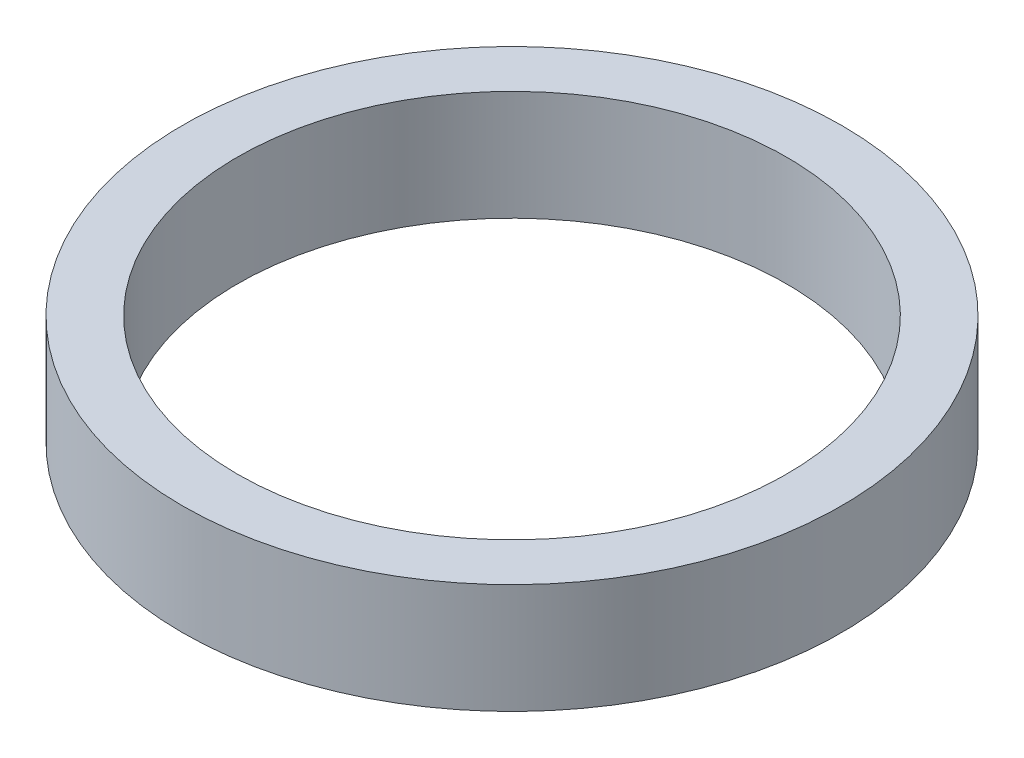
SolidWorks part; units mm, degrees
ref_plane "Front Plane" through (0, 0, 0) normal (0, 0, 1) x (1, 0, 0)
ref_plane "Top Plane" through (0, 0, 0) normal (0, 1, 0) x (1, 0, 0)
ref_plane "Right Plane" through (0, 0, 0) normal (1, 0, 0) x (0, 0, -1)
sketch "Sketch1" plane through (0, 0, 0) normal (0, 1, 0) x (1, 0, 0)
  circle A0 centre (0, 0) radius 45
  dimension "FLANGE_OD" = 90
extrude "Boss-Extrude1" add sketch "Sketch1" along normal blind 15
sketch "Sketch2" plane through (0, 0, 0) normal (0, 1, 0) x (1, 0, 0)
  circle A0 centre (0, 0) radius 37.5
  dimension "BORE_D" = 75
extrude "Cut-Extrude1" cut sketch "Sketch2" along normal through all
sketch "Sketch3" plane through (0, 15, 0) normal (0, 1, 0) x (1, 0, 0)
  circle A0 centre (0, 0) radius 20.8925 construction
  circle A1 centre (-20.8925, 0) radius 1.5
  dimension "BOLT_D" = 3
  dimension "BOLT_PCD" = 41.785
extrude "Cut-Extrude2" cut sketch "Sketch3" against normal blind 9.2454 rebuild error yes
pattern_circular "CirPattern1" count 4 over 360 rebuild error yes
